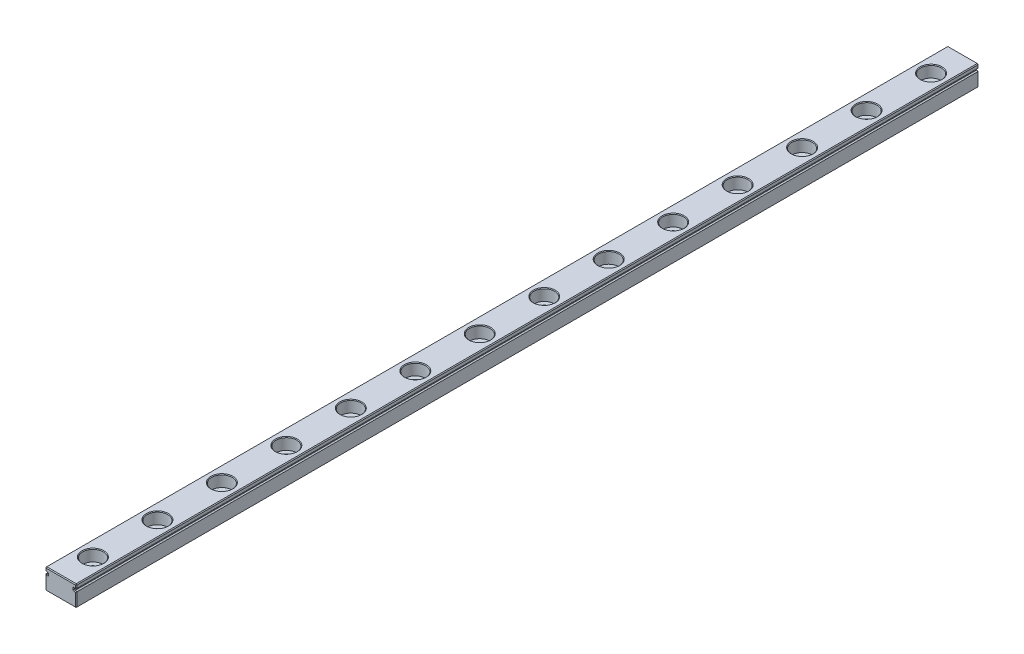
SolidWorks part; units mm, degrees
material "1.4310 (X10CrNi18-8)"
ref_plane "Front Plane" through (0, 0, 0) normal (0, 0, 1) x (1, 0, 0)
ref_plane "Top Plane" through (0, 0, 0) normal (0, 1, 0) x (1, 0, 0)
ref_plane "Right Plane" through (0, 0, 0) normal (1, 0, 0) x (0, 0, -1)
sketch "Sketch1" plane through (0, 0, 0) normal (0, 0, 1) x (1, 0, 0)
  line L0 (0, 0) -> (0, 8) construction
  line L1 (0, 8) -> (12, 8)
  line L2 (0, 0) -> (12, 0)
  line L3 (0, 8) -> (0, 6.75)
  line L4 (0, 6.75) -> (0.5, 6.25) construction
  line L5 (0.5, 6.25) -> (1, 6.25)
  line L6 (0.5, 5.75) -> (0, 5.25) construction
  line L7 (0, 5.25) -> (0, 0)
  line L8 (1, 6.25) -> (1, 5.75)
  line L9 (1, 5.75) -> (0.5, 5.75)
  line L10 (0.5, 5.75) -> (0.75, 6) construction
  line L11 (0.75, 6) -> (0.5, 6.25) construction
  line L12 (0, 6.75) -> (0, 6.559)
  line L13 (0, 5.25) -> (0, 5.441)
  line L14 (6, 8) -> (6, 0) construction
  line L15 (11.25, 6) -> (11.5, 6.25) construction
  line L16 (11.5, 5.75) -> (11.25, 6) construction
  line L17 (11.5, 5.75) -> (12, 5.25) construction
  line L18 (12, 6.75) -> (11.5, 6.25) construction
  line L19 (12, 0) -> (12, 8) construction
  line L20 (12, 5.25) -> (12, 5.441)
  line L21 (12, 6.75) -> (12, 6.559)
  line L22 (11, 5.75) -> (11.5, 5.75)
  line L23 (11, 6.25) -> (11, 5.75)
  line L24 (12, 5.25) -> (12, 0)
  line L25 (11.5, 6.25) -> (11, 6.25)
  line L26 (12, 8) -> (12, 6.75)
  arc A0 (0, 5.441) -> (0.5, 5.75) centre (0, 6) ccw
  arc A1 (0.5, 6.25) -> (0, 6.559) centre (0, 6) ccw
  arc A2 (11.5, 6.25) -> (12, 6.559) centre (12, 6) cw
  arc A3 (12, 5.441) -> (11.5, 5.75) centre (12, 6) cw
  point P4 (1, 6)
  point P28 (11, 6)
  dimension "D1" = 8
  dimension "D2" = 6
  dimension "D3" = 0.5
  dimension "D4" = 45
  dimension "D5" = 2
  dimension "D6" = 1
extrude "Boss-Extrude1" add sketch "Sketch1" along normal blind 350
chamfer "Chamfer1" distance 0.3 angle 45 36 edges at (0, 0, 175) (12, 0, 175) (0, 8, 175) (12, 8, 175) (0.2939, 5.5245, 350) (0.75, 5.75, 350) (1, 6, 350) (0.75, 6.25, 350) (0.2939, 6.4755, 350) (0, 7.2795, 350) (6, 8, 350) (12, 7.2795, 350) (11.7061, 6.4755, 350) (11.25, 6.25, 350) (11, 6, 350) (11.25, 5.75, 350) (11.7061, 5.5245, 350) (12, 2.7205, 350) (6, 0, 350) (0, 2.7205, 350) (12, 2.7205, 0) (11.7061, 5.5245, 0) (11.25, 5.75, 0) (11, 6, 0) (11.25, 6.25, 0) (11.7061, 6.4755, 0) (12, 7.2795, 0) (6, 0, 0) (0, 2.7205, 0) (0.2939, 5.5245, 0) (0.75, 5.75, 0) (1, 6, 0) (0.75, 6.25, 0) (0.2939, 6.4755, 0) (0, 7.2795, 0) (6, 8, 0)
hole_wizard "CBORE for M5 Hex Head Bolt1" positions "3DSketch1" profile "Sketch3" counterbore size "M5" standard "ANSI Metric" end condition through all
sketch3d "3DSketch1"
  line L0 (6, 8, 0) -> (6, 8, 12.5) construction
  line L1 (11.7, 8, 0) -> (0.3, 8, 0) construction
  point P0 (6, 8, 12.5)
  dimension "D1" = 12.5
sketch "Sketch3" plane through (6, 8, 12.5) normal (1, 0, 0) x (0, 0, 1)
  line L0 (0, 0) -> (0, 8)
  line L1 (2.25, 7.75) -> (2.5, 8)
  line L2 (4, 4.5) -> (2.25, 4.5)
  line L3 (2.25, 4.5) -> (2.25, 7.75)
  line L5 (4, 4.5) -> (4, 0.25)
  line L6 (4, 0.25) -> (4.25, 0)
  line L7 (4.25, 0) -> (0, 0)
  line L8 (-4, 0.25) -> (-4.25, 0) construction
  line L11 (0, -6.35) -> (0, 107.95) construction
  line L12 (2.5, 8) -> (0, 8)
  line L13 (-2.25, 7.75) -> (-2.5, 8) construction
  dimension "Thru Hole Dia." = 4.5
  dimension "Thru Hole Depth" = 8
  dimension "C'Bore Dia." = 8
  dimension "C'Bore Depth" = 4.5
  dimension "Near C'Sink Dia." = 8.5
  dimension "Near C'Sink Angle" = 90
  dimension "Far C'Sink Dia." = 5
  dimension "Far C'Sink Angle" = 90
pattern_linear "LPattern1" count 14 spacing 25 along (0, 0, 1) of "CBORE for M5 Hex Head Bolt1"
